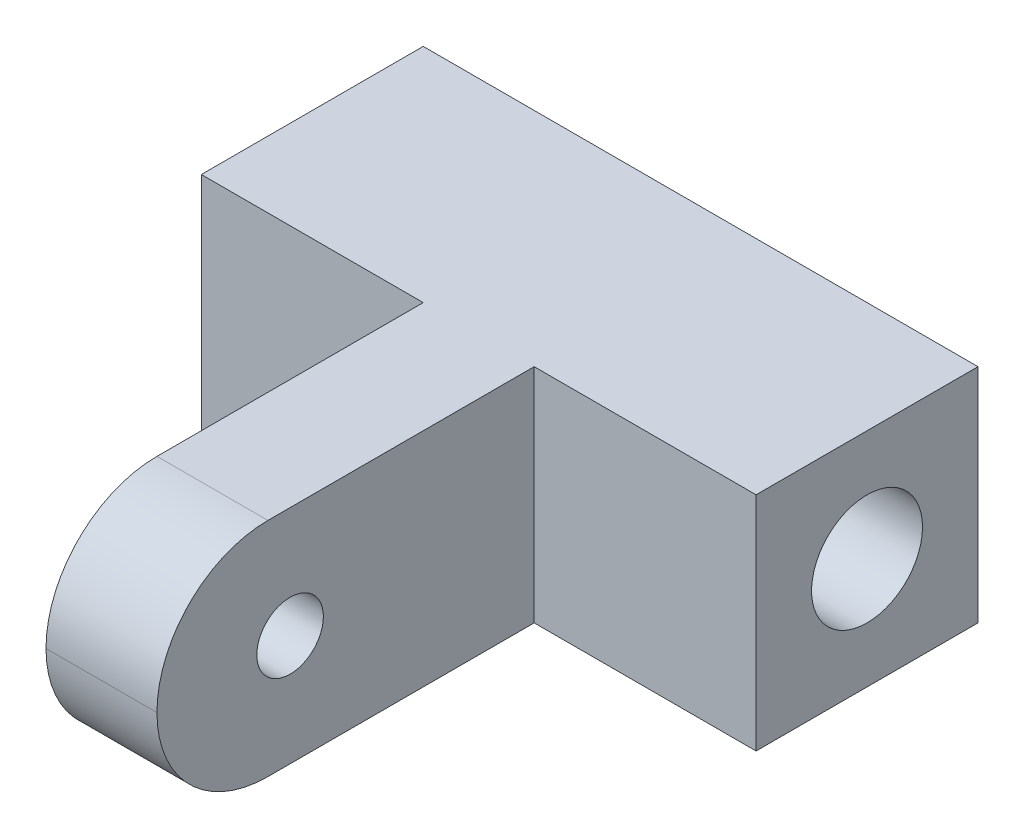
SolidWorks part; units mm, degrees
ref_plane "Front Plane" through (0, 0, 0) normal (0, 0, 1) x (1, 0, 0)
ref_plane "Top Plane" through (0, 0, 0) normal (0, 1, 0) x (1, 0, 0)
ref_plane "Right Plane" through (0, 0, 0) normal (1, 0, 0) x (0, 0, -1)
sketch "Sketch1" plane through (0, 0, 0) normal (0, 1, 0) x (1, 0, 0)
  line L0 (2.5, 0) -> (-2.5, 0)
  line L1 (-2.5, 0) -> (-2.5, 17)
  line L2 (-2.5, 17) -> (-12.5, 17)
  line L3 (-12.5, 17) -> (-12.5, 27)
  line L4 (-12.5, 27) -> (12.5, 27)
  line L5 (12.5, 27) -> (12.5, 17)
  line L6 (12.5, 17) -> (2.5, 17)
  line L7 (2.5, 17) -> (2.5, 0)
  point P4 (0, 0)
  dimension "D1" = 17
  dimension "D2" = 5
  dimension "D3" = 10
  dimension "D4" = 25
extrude "Boss-Extrude1" add sketch "Sketch1" along normal blind 10
sketch "Sketch2" plane through (12.5, 0, 0) normal (1, 0, 0) x (0, 0, -1)
  line L0 (0, 10) -> (0, 0) construction
  line L1 (0, 10) -> (17, 10) construction
  line L2 (27, 10) -> (27, 0) construction
  circle A0 centre (22, 5) radius 2.5
  circle A1 centre (6, 5) radius 1.5
  point P6 (0, 5)
  point P9 (8.5, 10)
  point P10 (0, 0)
  dimension "D1" = 5
  dimension "D2" = 3
  dimension "D3" = 5
  dimension "D4" = 6
extrude "Cut-Extrude1" cut sketch "Sketch2" against normal through all
fillet "Fillet1" radius 5 2 edges at (0, 10, 0) (0, 0, 0)
